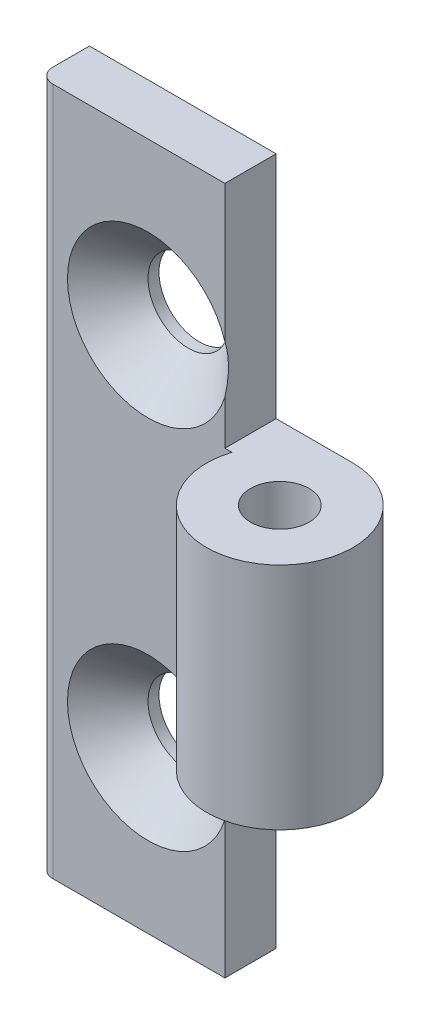
SolidWorks part; units mm, degrees
ref_plane "Front Plane" through (0, 0, 0) normal (0, 0, 1) x (1, 0, 0)
ref_plane "Top Plane" through (0, 0, 0) normal (0, 1, 0) x (1, 0, 0)
ref_plane "Right Plane" through (0, 0, 0) normal (1, 0, 0) x (0, 0, -1)
ref_plane "Plane1" through (0, 0, 0) normal (0, 0, 1) x (1, 0, 0)
sketch "Sketch1" plane through (0, 0, 0) normal (0, 0, 1) x (1, 0, 0)
  line L0 (0, 23.5) -> (5, 23.5)
  line L1 (5, 23.5) -> (5, -23.5)
  line L2 (5, -23.5) -> (0, -23.5)
  line L3 (0, -23.5) -> (0, 23.5)
  line L4 (0, -23.5) -> (0, 23.5) construction
revolve "Revolve1" add sketch "Sketch1" angle 360 about L4 reverse direction yes
ref_plane "Plane2" through (0, 0, -5) normal (0, 0, 1) x (1, 0, 0)
sketch "Sketch2" plane through (0, 0, -5) normal (0, 0, 1) x (1, 0, 0)
  line L0 (-18, -23.5) -> (0, -23.5)
  line L1 (0, -23.5) -> (0, 23.5)
  line L2 (0, 23.5) -> (-18, 23.5)
  line L3 (-18, 23.5) -> (-18, -23.5)
extrude "Boss-Extrude1" add sketch "Sketch2" along normal blind 3.5
ref_plane "Plane3" through (0, 0, 0) normal (0, 0, 1) x (1, 0, 0)
sketch "Sketch3" plane through (0, 0, 0) normal (0, 0, 1) x (1, 0, 0)
  line L0 (-47, -47) -> (47, -47)
  line L1 (47, -47) -> (47, 47)
  line L2 (47, 47) -> (-47, 47)
  line L3 (-47, 47) -> (-47, -47)
  line L4 (-18, -23.5) -> (-5.25, -23.5)
  line L5 (-5.25, -23.5) -> (-5.25, -7.8333)
  line L6 (-5.25, -7.8333) -> (5, -7.8333)
  line L7 (5, -7.8333) -> (5, 7.8333)
  line L8 (5, 7.8333) -> (-5.25, 7.8333)
  line L9 (-5.25, 7.8333) -> (-5.25, 23.5)
  line L10 (-5.25, 23.5) -> (-18, 23.5)
  line L11 (-18, 23.5) -> (-18, -23.5)
extrude "Cut-Extrude1" cut sketch "Sketch3" against normal blind 47 and the other way blind 47
ref_plane "Plane4" through (0, 0, 0) normal (0, 0, 1) x (1, 0, 0)
sketch "Sketch4" plane through (0, 0, 0) normal (0, 0, 1) x (1, 0, 0)
  line L0 (0, 26.7) -> (2, 26.7)
  line L1 (2, 26.7) -> (2, -26.7)
  line L2 (2, -26.7) -> (0, -26.7)
  line L3 (0, -26.7) -> (0, 26.7)
  line L4 (0, -26.7) -> (0, 26.7) construction
revolve "Cut-Revolve1" cut sketch "Sketch4" angle 360 about L4 reverse direction yes
ref_plane "Plane5" through (-10.5, 0, 0) normal (1, 0, 0) x (0, 0, -1)
sketch "Sketch5" plane through (-10.5, 0, 0) normal (1, 0, 0) x (0, 0, -1)
  line L0 (5, -12.5) -> (5, -15.25)
  line L1 (5, -15.25) -> (4.25, -15.25)
  line L2 (4.25, -15.25) -> (1.5, -18)
  line L3 (1.5, -18) -> (1.5, -12.5)
  line L4 (1.5, -12.5) -> (5, -12.5)
  line L5 (1.5, -12.5) -> (5, -12.5) construction
revolve "Cut-Revolve2" cut sketch "Sketch5" angle 360 about L5 reverse direction yes
ref_plane "Plane6" through (-10.5, 0, 0) normal (1, 0, 0) x (0, 0, -1)
sketch "Sketch6" plane through (-10.5, 0, 0) normal (1, 0, 0) x (0, 0, -1)
  line L0 (5, 12.5) -> (5, 9.75)
  line L1 (5, 9.75) -> (4.25, 9.75)
  line L2 (4.25, 9.75) -> (1.5, 7)
  line L3 (1.5, 7) -> (1.5, 12.5)
  line L4 (1.5, 12.5) -> (5, 12.5)
  line L5 (1.5, 12.5) -> (5, 12.5) construction
revolve "Cut-Revolve3" cut sketch "Sketch6" angle 360 about L5 reverse direction yes
ref_plane "Plane7" through (0, 0, 0) normal (0, 1, 0) x (1, 0, 0)
sketch "Sketch7" plane through (0, 0, 0) normal (0, 1, 0) x (1, 0, 0)
  line L0 (-18, 1.5) -> (-17, 1.5)
  line L1 (-18, 2.5) -> (-18, 1.5)
  arc A0 (-17, 1.5) -> (-18, 2.5) centre (-17, 2.5) cw
extrude "Cut-Extrude2" cut sketch "Sketch7" against normal blind 23.5 and the other way blind 23.5
